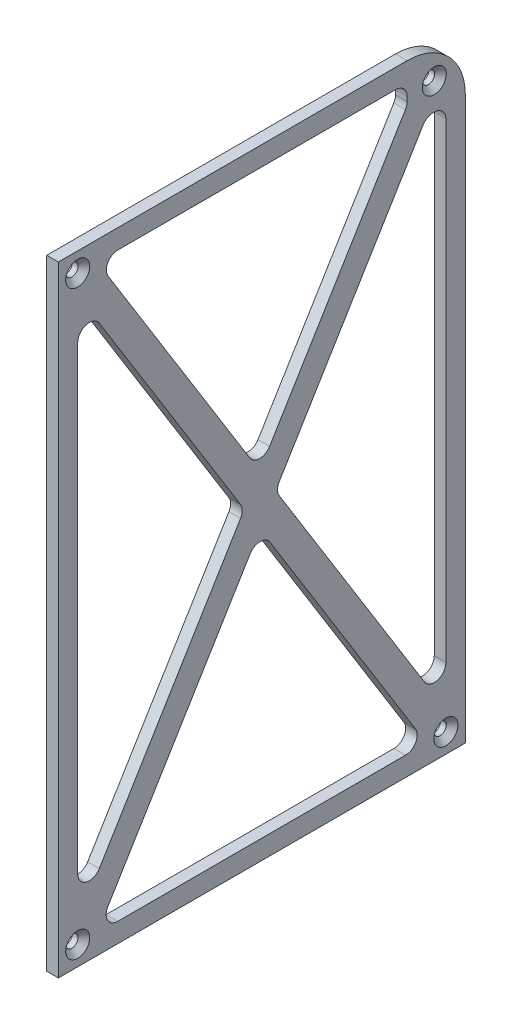
SolidWorks part; units mm, degrees
ref_plane "Front Plane" through (0, 0, 0) normal (0, 0, 1) x (1, 0, 0)
ref_plane "Top Plane" through (0, 0, 0) normal (0, 1, 0) x (1, 0, 0)
ref_plane "Right Plane" through (0, 0, 0) normal (1, 0, 0) x (0, 0, -1)
sketch "Sketch1" plane through (0, 0, 0) normal (1, 0, 0) x (0, 0, -1)
  line L0 (5, 5) -> (5, 6.6)
  line L1 (0, 0) -> (105, 0)
  line L2 (0, 0) -> (0, 160)
  line L3 (0, 160) -> (90, 160)
  line L4 (105, 0) -> (105, 145)
  line L5 (5, 155) -> (6.6, 155)
  line L6 (100, 5) -> (100, 6.6)
  line L7 (5, 5) -> (6.6, 5)
  line L8 (10, 155) -> (90, 155)
  line L9 (5, 153.4) -> (5, 155)
  line L10 (5, 155) -> (90, 155) construction
  line L11 (5, 10) -> (5, 150)
  line L12 (5, 5) -> (5, 155) construction
  line L13 (10, 5) -> (95, 5)
  line L14 (98.4, 5) -> (100, 5)
  line L15 (5, 5) -> (100, 5) construction
  line L16 (100, 10) -> (100, 145)
  line L17 (0, 160) -> (131.8816, 160) construction
  line L18 (100, 5) -> (100, 145) construction
  line L19 (105, 0) -> (105, 197.6676) construction
  line L20 (5, 150) -> (47.9689, 80.7723)
  line L21 (100, 10) -> (56.0381, 80.8275)
  line L22 (90, 145) -> (117.2655, 145) construction
  line L23 (90, 145) -> (109.727, 164.727) construction
  line L24 (90, 155) -> (90, 150)
  line L25 (95, 145) -> (100, 145)
  line L26 (5, 10) -> (47.9689, 80.7723)
  line L27 (10, 5) -> (52.0311, 74.2277)
  line L28 (51.9759, 87.3721) -> (90, 150)
  line L29 (51.9759, 87.3721) -> (10, 155)
  line L30 (56.0381, 80.8275) -> (95, 145)
  line L31 (52.0311, 74.2277) -> (95, 5)
  circle A0 centre (5, 155) radius 1.6
  circle A1 centre (97, 152) radius 1.6
  circle A2 centre (100, 5) radius 1.6
  circle A3 centre (5, 5) radius 1.6
  arc A4 (90, 160) -> (105, 145) centre (90, 145) cw
  arc A5 (90, 155) -> (100, 145) centre (90, 145) cw construction
  dimension "D3" = 15
  dimension "D5" = 3.2
  dimension "D6" = 3.2
  dimension "D7" = 3.2
  dimension "D8" = 3.2
  dimension "D1" = 105
  dimension "D2" = 160
  dimension "D9" = 5
  dimension "D10" = 5
  dimension "D11" = 5
  dimension "D12" = 5
  dimension "D13" = 5
  dimension "D14" = 5
  dimension "D15" = 10
  dimension "D16" = 10
  dimension "D17" = 10
  dimension "D18" = 10
  dimension "D19" = 45
  dimension "D20" = 8
  dimension "D21" = 10
  dimension "D22" = 10
  dimension "D23" = 10
  dimension "D24" = 10
  dimension "D4" = 5
extrude "Boss-Extrude2" add sketch "Sketch1" along normal blind 3 contours A4 L3 L2 L1 L4 L5 A5 L6 A2 L7 A3 L0 region at (0, 79.7352, -52.0977)
fillet "Fillet1" radius 3 14 edges at (1.5, 10, -100) (1.5, 150, -5) (1.5, 145, -100) (1.5, 155, -90) (1.5, 10, -5) (1.5, 5, -10) (1.5, 5, -95) (1.5, 155, -10) (1.5, 150, -90) (1.5, 145, -95) (1.5, 80.7723, -47.9689) (1.5, 74.2277, -52.0311) (1.5, 80.8275, -56.0381) (1.5, 87.3721, -51.9759)
chamfer "Chamfer1" distance 1.5 angle 45 4 edges at (3, 5, -101.6) (3, 5, -6.6) (3, 152, -98.6) (3, 155, -6.6)
